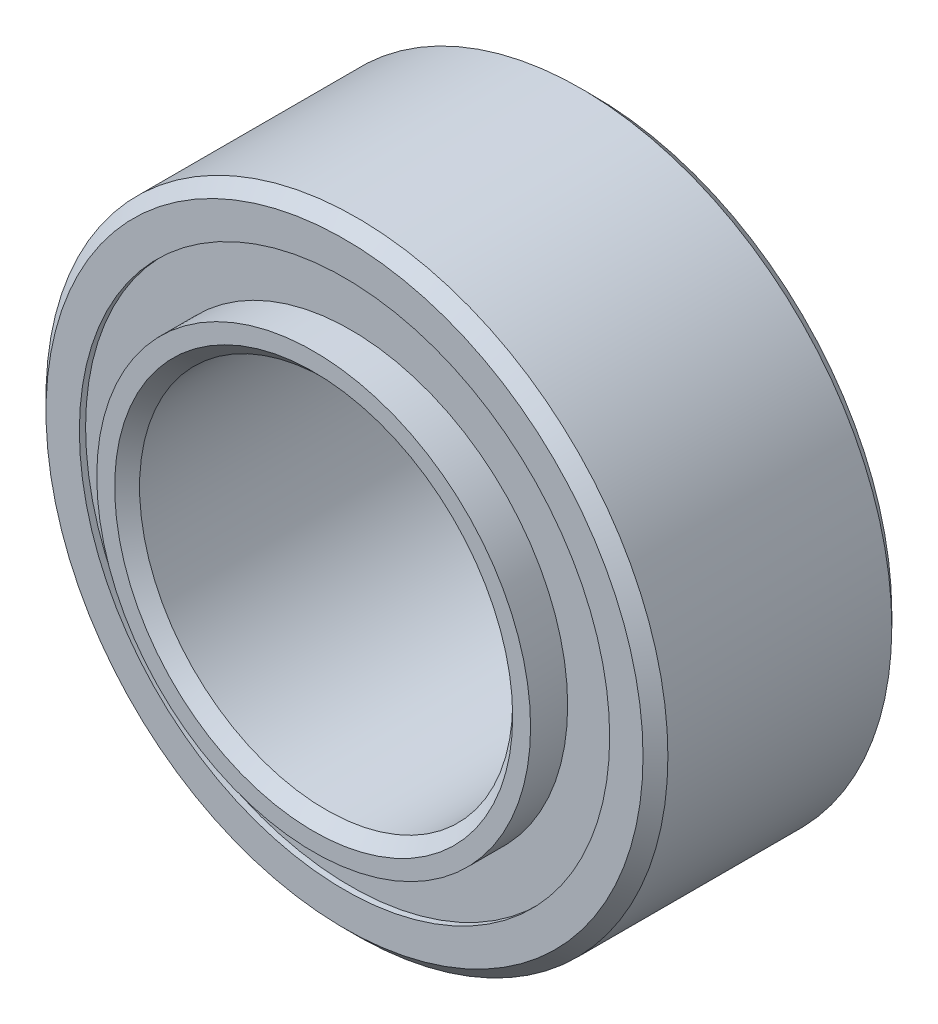
SolidWorks part; units mm, degrees
ref_plane "Front Plane" through (0, 0, 0) normal (0, 0, 1) x (1, 0, 0)
ref_plane "Top Plane" through (0, 0, 0) normal (0, 1, 0) x (1, 0, 0)
ref_plane "Right Plane" through (0, 0, 0) normal (1, 0, 0) x (0, 0, -1)
sketch "Sketch1" plane through (0, 0, 0) normal (1, 0, 0) x (0, 0, -1)
  line L0 (-1.5875, 0) -> (1.5875, 0) construction
  line L1 (0, 3.9688) -> (0, -3.9688) construction
  line L2 (1.4288, 3.9688) -> (-1.4288, 3.9688)
  line L3 (-1.4288, 3.9688) -> (-1.5875, 3.81)
  line L4 (-1.5875, 3.81) -> (-1.5875, 3.3843)
  line L5 (-1.5875, 3.3843) -> (-0.7056, 3.3843)
  line L6 (1.5875, 3.3843) -> (0.7056, 3.3843)
  line L7 (1.5875, 3.81) -> (1.5875, 3.3843)
  line L8 (1.4288, 3.9688) -> (1.5875, 3.81)
  line L9 (0, 3.9688) -> (0, 3.175) construction
  line L10 (0, 3.175) -> (0, 2.3813) construction
  arc A0 (-0.7056, 3.3843) -> (0.7056, 3.3843) centre (0, 3.175) cw
  point P14 (0, 2.3813)
  dimension "Width" = 3.175
  dimension "OD" = 7.9375
  dimension "D1" = 45
  dimension "D2" = 0.1588
  dimension "Shaft Dia" = 4.7625
  dimension "D3" = 1.4111
  dimension "D4" = 0.2093
revolve "Revolve1" add sketch "Sketch1" angle 360 about L0
sketch "Sketch3" plane through (0, 0, 0) normal (1, 0, 0) x (0, 0, -1)
  line L0 (-0.7056, 2.9657) -> (-1.9812, 2.9657) construction
  line L1 (-1.5875, 3.81) -> (-1.5875, 3.3843) construction
  line L2 (-1.4288, 3.9688) -> (-1.5875, 3.81) construction
  line L3 (-1.9812, 2.9657) -> (-1.9812, 2.54) construction
  line L4 (-1.9812, 2.54) -> (-1.9812, 2.7686)
  line L5 (-1.9812, 2.54) -> (-1.8225, 2.3813)
  line L6 (-1.8225, 2.3813) -> (1.8225, 2.3812)
  line L7 (-1.9812, 2.7686) -> (1.9812, 2.7686)
  line L8 (1.8225, 2.3812) -> (1.9812, 2.54)
  line L9 (-1.5875, 0) -> (1.3916, 0) construction
  line L10 (1.9812, 2.54) -> (1.9812, 2.9657) construction
  line L11 (1.9812, 2.9657) -> (0.7056, 2.9657) construction
  line L12 (0, 3.9688) -> (0, -3.9688) construction
  line L13 (1.4288, 3.9688) -> (1.5875, 3.81) construction
  line L18 (1.9812, 2.7686) -> (1.9812, 2.54)
  arc A1 (0.7056, 2.9657) -> (-0.7056, 2.9657) centre (0, 3.175) cw construction
  arc A2 (0.7056, 3.3843) -> (-0.7056, 3.3843) centre (0, 3.175) ccw construction
  dimension "D1" = 45
  dimension "Ring" = 3.9624
  dimension "D2" = 5.5372
revolve "Revolve3" add sketch "Sketch3" angle 360 about L0
sketch "Sketch4" plane through (0, 0, 0) normal (1, 0, 0) x (0, 0, -1)
  line L0 (-0.736, 3.175) -> (0.736, 3.175)
  arc A2 (-0.736, 3.175) -> (0.736, 3.175) centre (0, 3.175) cw
  arc A3 (0.7056, 3.3843) -> (-0.7056, 3.3843) centre (0, 3.175) ccw construction
revolve "Revolve4" add sketch "Sketch4" angle 360 about L0
ref_axis "Axis1" through (0, 0, -1.5875) along (0, 0, 1)
pattern_circular "CirPattern1" count 10 every 36 about axis through (0, 0, -1.5875) along (0, 0, 1) of bodies 104
sketch "Sketch5" plane through (0, 0, 0) normal (1, 0, 0) x (0, 0, -1)
  line L0 (-1.5875, 3.3843) -> (-0.7056, 3.3843) construction
  line L1 (-1.5081, 3.3843) -> (-0.736, 3.3843)
  line L2 (-1.5081, 3.3843) -> (-1.5081, 2.7686)
  line L3 (-1.5081, 2.7686) -> (-0.736, 2.7686)
  line L4 (-0.736, 3.3843) -> (-0.736, 2.7686)
  line L5 (-1.9812, 2.7686) -> (1.9812, 2.7686) construction
  line L6 (1.5875, 3.3843) -> (0.7056, 3.3843) construction
  line L7 (1.5081, 3.3843) -> (0.736, 3.3843)
  line L8 (1.5081, 3.3843) -> (1.5081, 2.7686)
  line L9 (1.5081, 2.7686) -> (0.736, 2.7686)
  line L10 (0.736, 3.3843) -> (0.736, 2.7686)
  line L12 (-1.4288, 3.9688) -> (-1.5875, 3.81) construction
  point P18 (-1.5081, 3.8894)
revolve "Revolve5" add sketch "Sketch5" angle 360 about L0
equation "\"D2@Sketch1\" = \"Width@Sketch1\"*.05"
equation "\"D3@Sketch1\" = \"Width@Sketch1\"/2.25"
equation "\"D4@Sketch1\" = (((\"OD@Sketch1\"-\"Width@Sketch1\")/2)/3.25)/3.5"
equation "\"D2@CirPattern1\" = 360/\"Balls@CirPattern1\""
